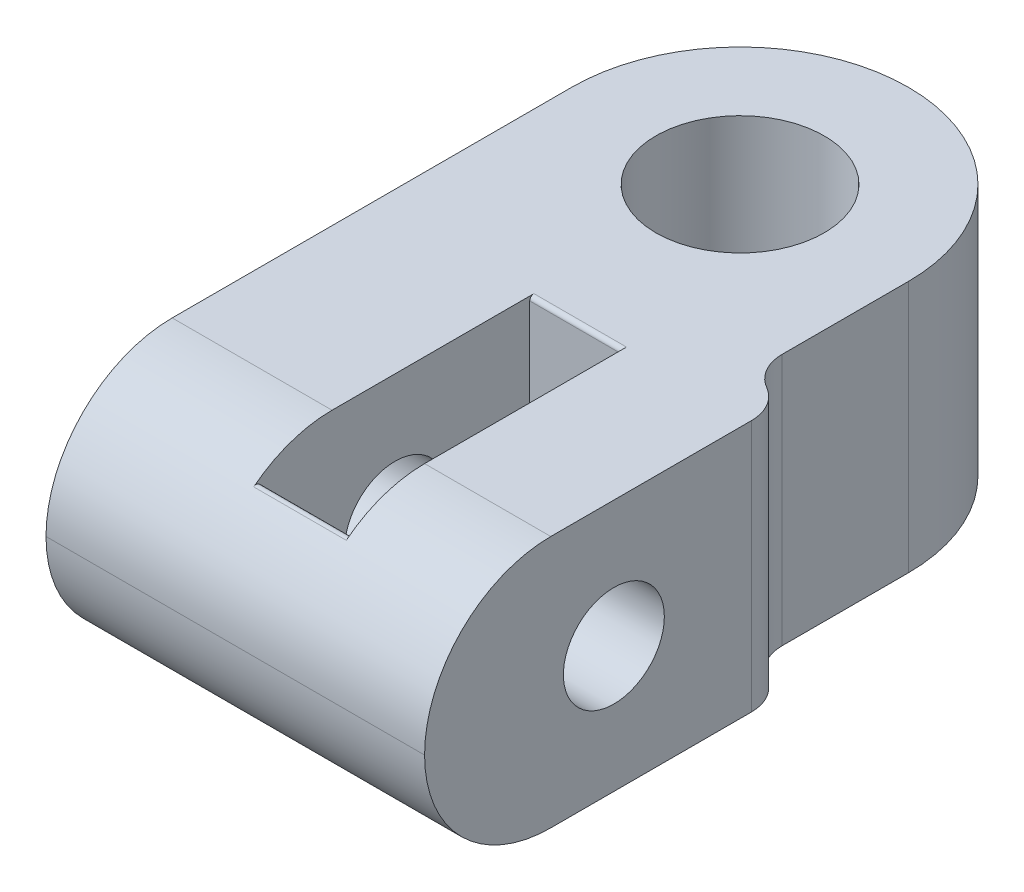
SolidWorks part; units mm, degrees
ref_plane "Front Plane" through (0, 0, 0) normal (0, 0, 1) x (1, 0, 0)
ref_plane "Top Plane" through (0, 0, 0) normal (0, 1, 0) x (1, 0, 0)
ref_plane "Right Plane" through (0, 0, 0) normal (1, 0, 0) x (0, 0, -1)
sketch "Sketch1" plane through (0, 0, 0) normal (0, 1, 0) x (1, 0, 0)
  line L0 (-5.08, 5.08) -> (5.08, 5.08)
  line L1 (5.08, 5.08) -> (5.08, -5.08)
  line L2 (5.08, -5.08) -> (6.35, -5.08)
  line L3 (6.35, -5.08) -> (6.35, -15.875)
  line L4 (6.35, -15.875) -> (-5.08, -15.875)
  line L5 (-5.08, -15.875) -> (-5.08, 5.08)
  circle A0 centre (0, 0) radius 2.54
  point P5 (5.08, 0)
  point P10 (0, 5.08)
  dimension "D1" = 5.08
  dimension "D2" = 10.16
  dimension "D3" = 10.16
  dimension "D4" = 10.795
  dimension "D5" = 11.43
extrude "Boss-Extrude1" add sketch "Sketch1" along normal blind 7.62
sketch "Sketch2" plane through (6.35, 0, 0) normal (1, 0, 0) x (0, 0, -1)
  line L0 (-15.875, 7.62) -> (-15.875, 0) construction
  line L2 (-5.08, 7.62) -> (-5.08, 0) construction
  circle A0 centre (-10.16, 3.81) radius 1.524
  point P4 (-15.875, 3.81)
  dimension "D1" = 3.048
  dimension "D2" = 5.08
extrude "Cut-Extrude1" cut sketch "Sketch2" against normal through all
fillet "Fillet1" radius 5.08 2 edges at (-5.08, 3.81, -5.08) (5.08, 3.81, -5.08)
fillet "Fillet4" radius 3.81 2 edges at (0.635, 0, 15.875) (0.635, 7.62, 15.875)
fillet "Fillet2" radius 1.27 1 edges at (5.08, 3.81, 5.08)
fillet "Fillet3" radius 1.27 1 edges at (6.35, 3.81, 5.08)
ref_axis "Axis1" through (-5.08, 3.81, 10.16) along (1, 0, 0)
sketch "Sketch3" plane through (0, 7.62, 0) normal (0, 1, 0) x (1, 0, 0)
  line L0 (-5.08, -10.16) -> (6.35, -10.16) construction
  line L1 (-0.254, -14.224) -> (2.54, -14.224)
  line L2 (-0.254, -14.224) -> (-0.254, -6.096)
  line L3 (-0.254, -6.096) -> (2.54, -6.096)
  line L4 (2.54, -14.224) -> (2.54, -6.096)
  line L5 (-0.254, -14.224) -> (2.54, -6.096) construction
  line L6 (-0.254, -6.096) -> (2.54, -14.224) construction
  line L7 (6.35, -12.065) -> (6.35, -6.0097) construction
  point P0 (1.143, -10.16)
  dimension "D1" = 8.128
  dimension "D2" = 2.794
  dimension "D3" = 3.81
extrude "Cut-Extrude2" cut sketch "Sketch3" against normal through all
fillet "Fillet5" radius 0.127 4 edges at (1.143, 0, 6.096) (1.143, 7.62, 6.096) (1.143, 0.6708, 14.224) (1.143, 6.9492, 14.224)
